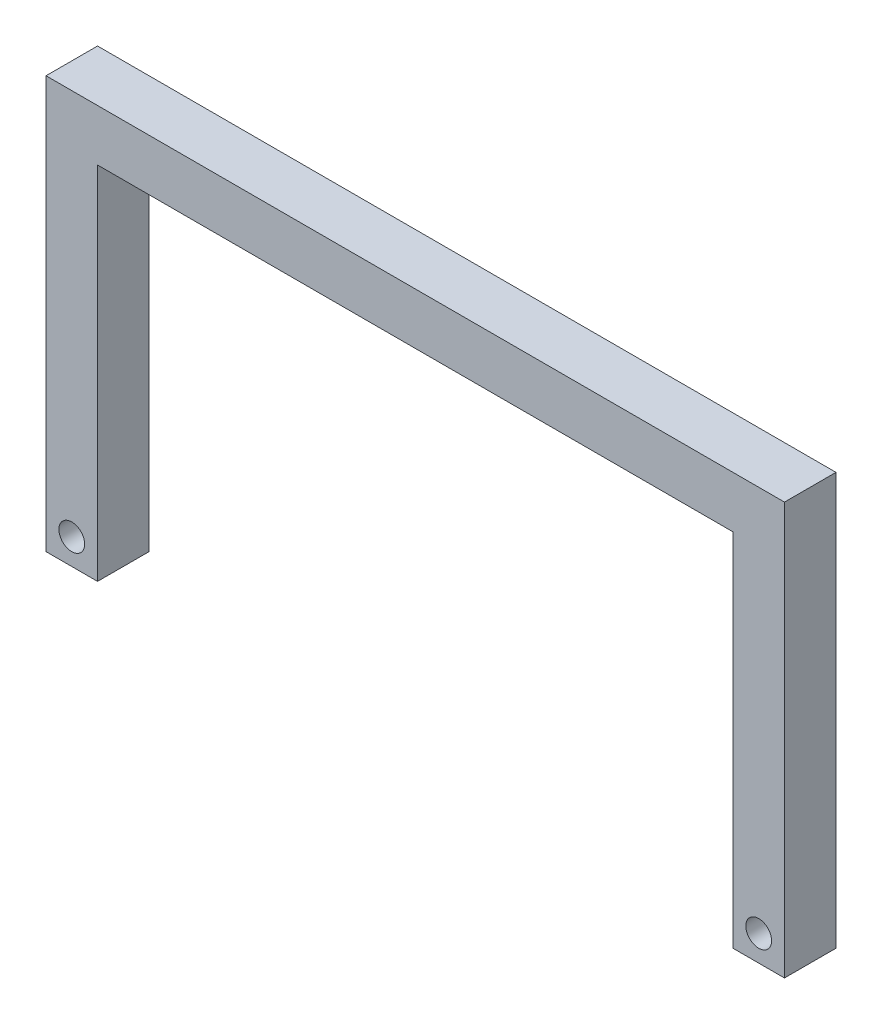
SolidWorks part; units mm, degrees
material "1060 Alloy for 162A"
ref_plane "Front Plane" through (0, 0, 0) normal (0, 0, 1) x (1, 0, 0)
ref_plane "Top Plane" through (0, 0, 0) normal (0, 1, 0) x (1, 0, 0)
ref_plane "Right Plane" through (0, 0, 0) normal (1, 0, 0) x (0, 0, -1)
sketch "Sketch1" plane through (0, 0, 0) normal (0, 0, 1) x (1, 0, 0)
  line L0 (-185, -15) -> (-185, -225)
  line L1 (215, 15) -> (-215, 15)
  line L2 (215, 15) -> (215, -15)
  line L4 (-215, 15) -> (-215, -15)
  line L5 (215, 15) -> (-215, -15) construction
  line L6 (215, -15) -> (-215, 15) construction
  line L8 (-215, 15) -> (-215, -225)
  line L9 (-215, -225) -> (-185, -225)
  line L12 (215, 15) -> (215, -225)
  line L13 (215, -225) -> (185, -225)
  line L15 (185, -15) -> (185, -225)
  line L16 (185, -15) -> (-185, -15)
  circle A0 centre (-200, -210) radius 7.5
  circle A1 centre (200, -210) radius 7.5
  point P0 (0, 0)
  point P8 (215, 15)
  point P14 (0, 0)
  point P17 (-200, -225)
  point P18 (0, 0)
  point P19 (200, -225)
  point P20 (0, 0)
  point P21 (0, 0)
  point P23 (-16.8581, -27.3525)
  point P25 (234.8734, -59.1062)
  point P26 (184.5843, -37.122)
  point P27 (-185, -5.2158)
  point P28 (-92.7438, 15)
  point P29 (-356.1422, 15)
  point P30 (274.8308, 15)
  dimension "D2" = 15
  dimension "D1" = 30
  dimension "D4" = 15
  dimension "D5" = 400
  dimension "D3" = 240
extrude "Boss-Extrude1" add sketch "Sketch1" along normal mid plane 30 contours L16 L15 L13 L12 L2 L1 L4 L8 L9 L0 A1 A0 region at (-189.9244, -120, 0)
equation "\"table_height\"=50"
equation "\"A\"= 200"
equation "\"r6\"=400"
equation "\"D5@Sketch1\"=\"r6\""
equation "\"h6\"=240"
equation "\"D3@Sketch1\"=\"h6\""
